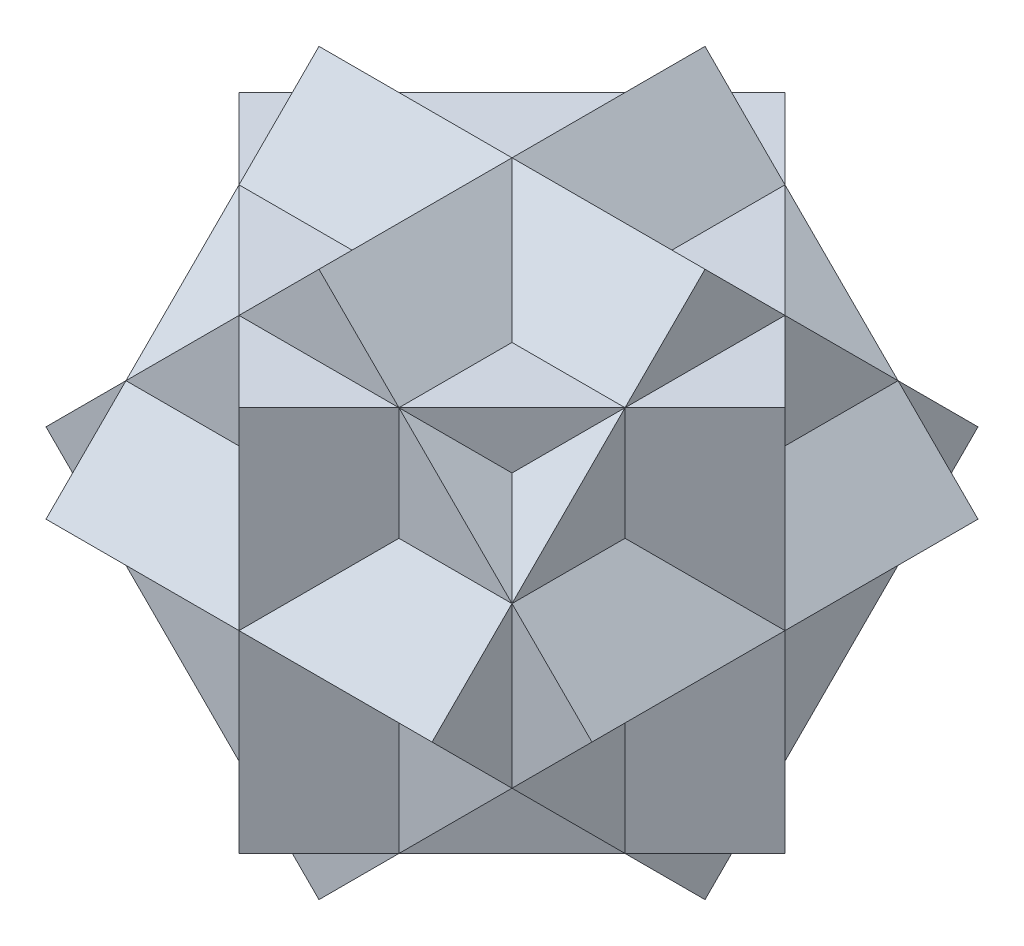
SolidWorks part; units mm, degrees
ref_plane "Front Plane" through (0, 0, 0) normal (0, 0, 1) x (1, 0, 0)
ref_plane "Top Plane" through (0, 0, 0) normal (0, 1, 0) x (1, 0, 0)
ref_plane "Right Plane" through (0, 0, 0) normal (1, 0, 0) x (0, 0, -1)
sketch "Sketch3" plane through (0, 0, 0) normal (0, 0, 1) x (1, 0, 0)
  line L0 (-160.803, 0) -> (0, 160.803)
  line L1 (-160.803, 0) -> (0, -160.803)
  line L2 (0, 160.803) -> (160.803, 0)
  line L3 (0, -160.803) -> (160.803, 0)
  line L4 (-160.803, 0) -> (160.803, 0) construction
  line L5 (0, 160.803) -> (0, -160.803) construction
  point P1 (0, 0)
  dimension "D1" = 227.4098
sketch "Sketch4" plane through (0, 0, 0) normal (0, 1, 0) x (1, 0, 0)
  line L0 (-160.803, 0) -> (0, 160.803)
  line L1 (-160.803, 0) -> (0, -160.803)
  line L2 (0, 160.803) -> (160.803, 0)
  line L3 (0, -160.803) -> (160.803, 0)
  line L4 (-160.803, 0) -> (160.803, 0) construction
  line L5 (0, 160.803) -> (0, -160.803) construction
  point P1 (0, 0)
sketch "Sketch5" plane through (0, 0, 0) normal (1, 0, 0) x (0, 0, -1)
  line L0 (-160.803, 0) -> (0, 160.803)
  line L1 (-160.803, 0) -> (0, -160.803)
  line L2 (0, 160.803) -> (160.803, 0)
  line L3 (0, -160.803) -> (160.803, 0)
  line L4 (-160.803, 0) -> (160.803, 0) construction
  line L5 (0, 160.803) -> (0, -160.803) construction
  line L6 (0, 160.803) -> (0, -160.803) construction
  point P1 (0, 0)
extrude "Boss-Extrude1" add sketch "Sketch3" along normal mid plane 227.4098
extrude "Boss-Extrude2" add sketch "Sketch4" along normal mid plane 227.4098
extrude "Boss-Extrude3" add sketch "Sketch5" along normal mid plane 227.4098
sketch "Sketch6" plane through (80.4015, -80.4015, 0) normal (0.7071, -0.7071, 0) x (0, 0, -1)
  line L16 (-4.9069, -111.1649) -> (-48.4129, -49.6381)
  line L17 (-48.4129, -49.6381) -> (-111.1649, -49.6381)
  line L18 (-111.1649, -49.6381) -> (-111.1649, -111.1649)
  line L19 (-111.1649, -111.1649) -> (-4.9069, -111.1649)
  line L20 (-4.9069, -111.1649) -> (-48.4129, -49.6381)
  line L21 (-48.4129, -49.6381) -> (-111.1649, -49.6381)
  line L22 (-111.1649, -49.6381) -> (-111.1649, -111.1649)
  line L23 (-111.1649, -111.1649) -> (-4.9069, -111.1649)
  dimension "D2" = 2.54
sketch "Sketch8" plane through (-80.4015, -80.4015, 0) normal (-0.7071, -0.7071, 0) x (0, 0, 1)
  line L8 (48.4129, -49.6381) -> (4.9069, -111.1649)
  line L9 (4.9069, -111.1649) -> (111.1649, -111.1649)
  line L10 (111.1649, -111.1649) -> (111.1649, -49.6381)
  line L11 (111.1649, -49.6381) -> (48.4129, -49.6381)
  line L12 (48.4129, -49.6381) -> (4.9069, -111.1649)
  line L13 (4.9069, -111.1649) -> (111.1649, -111.1649)
  line L14 (111.1649, -111.1649) -> (111.1649, -49.6381)
  line L15 (111.1649, -49.6381) -> (48.4129, -49.6381)
  dimension "D1" = 2.54
sketch "Sketch11" plane through (0, 0, 113.7049) normal (0, 0, 1) x (1, 0, 0)
  line L0 (0, -157.2109) -> (40.966, -116.2449)
  line L1 (40.966, -116.2449) -> (-40.966, -116.2449)
  line L2 (-40.966, -116.2449) -> (0, -157.2109)
  line L3 (0, -160.803) -> (47.0981, -113.7049)
  line L4 (47.0981, -113.7049) -> (-47.0981, -113.7049)
  line L5 (-47.0981, -113.7049) -> (0, -160.803)
  line L6 (0, -160.803) -> (47.0981, -113.7049) construction
  line L7 (47.0981, -113.7049) -> (-47.0981, -113.7049) construction
  line L8 (-47.0981, -113.7049) -> (0, -160.803) construction
  dimension "D2" = 2.54
sketch "Sketch12" plane through (0, -113.7049, 0) normal (0, -1, 0) x (1, 0, 0)
  line L0 (0, 159.0069) -> (-44.0321, 114.9749)
  line L1 (-44.0321, 114.9749) -> (44.0321, 114.9749)
  line L2 (44.0321, 114.9749) -> (0, 159.0069)
  line L3 (-47.0981, 113.7049) -> (47.0981, 113.7049)
  line L4 (47.0981, 113.7049) -> (0, 160.803)
  line L5 (0, 160.803) -> (-47.0981, 113.7049)
  line L6 (-47.0981, 113.7049) -> (47.0981, 113.7049) construction
  line L7 (47.0981, 113.7049) -> (0, 160.803) construction
  line L8 (0, 160.803) -> (-47.0981, 113.7049) construction
  point P6 (0, 154.8281)
  dimension "D2" = 2.54
sketch "Sketch13" plane through (0, -80.4015, 80.4015) normal (0, -0.7071, 0.7071) x (1, 0, 0)
  line L0 (111.1649, -49.6381) -> (48.4129, -49.6381)
  line L1 (48.4129, -49.6381) -> (4.9069, -111.1649)
  line L2 (4.9069, -111.1649) -> (111.1649, -111.1649)
  line L3 (111.1649, -111.1649) -> (111.1649, -49.6381)
  line L4 (113.7049, -113.7049) -> (113.7049, -47.0981)
  line L5 (113.7049, -47.0981) -> (47.0981, -47.0981)
  line L6 (47.0981, -47.0981) -> (0, -113.7049)
  line L7 (0, -113.7049) -> (113.7049, -113.7049)
  line L8 (113.7049, -113.7049) -> (113.7049, -47.0981) construction
  line L9 (113.7049, -47.0981) -> (47.0981, -47.0981) construction
  line L10 (47.0981, -47.0981) -> (0, -113.7049) construction
  line L11 (0, -113.7049) -> (113.7049, -113.7049) construction
  dimension "D2" = 2.54
sketch "Sketch14" plane through (0, -113.7049, 0) normal (0, -1, 0) x (1, 0, 0)
  line L0 (49.6381, 107.5728) -> (49.6381, 49.6381)
  line L1 (49.6381, 49.6381) -> (107.5728, 49.6381)
  line L2 (107.5728, 49.6381) -> (49.6381, 107.5728)
  line L3 (47.0981, 47.0981) -> (113.7049, 47.0981)
  line L4 (113.7049, 47.0981) -> (47.0981, 113.7049)
  line L5 (47.0981, 113.7049) -> (47.0981, 47.0981)
  line L6 (47.0981, 47.0981) -> (113.7049, 47.0981) construction
  line L7 (113.7049, 47.0981) -> (47.0981, 113.7049) construction
  line L8 (47.0981, 113.7049) -> (47.0981, 47.0981) construction
  dimension "D2" = 2.54
sketch "Sketch15" plane through (80.4015, 0, 80.4015) normal (0.7071, 0, 0.7071) x (0.7071, 0, -0.7071)
  line L0 (39.1066, -111.1649) -> (0, -83.5123)
  line L1 (0, -83.5123) -> (-39.1066, -111.1649)
  line L2 (-39.1066, -111.1649) -> (39.1066, -111.1649)
  line L3 (47.0981, -113.7049) -> (0, -80.4015)
  line L4 (0, -80.4015) -> (-47.0981, -113.7049)
  line L5 (-47.0981, -113.7049) -> (47.0981, -113.7049)
  line L6 (47.0981, -113.7049) -> (0, -80.4015) construction
  line L7 (0, -80.4015) -> (-47.0981, -113.7049) construction
  line L8 (-47.0981, -113.7049) -> (47.0981, -113.7049) construction
  dimension "D2" = 2.54
sketch "Sketch16" plane through (80.4015, -80.4015, 0) normal (0.7071, -0.7071, 0) x (0, 0, -1)
  line L0 (-83.5123, 0) -> (-111.1649, 39.1066)
  line L1 (-111.1649, 39.1066) -> (-111.1649, -39.1066)
  line L2 (-111.1649, -39.1066) -> (-83.5123, 0)
  line L3 (-80.4015, 0) -> (-113.7049, 47.0981)
  line L4 (-113.7049, 47.0981) -> (-113.7049, -47.0981)
  line L5 (-113.7049, -47.0981) -> (-80.4015, 0)
  line L6 (-80.4015, 0) -> (-113.7049, 47.0981) construction
  line L7 (-113.7049, 47.0981) -> (-113.7049, -47.0981) construction
  line L8 (-113.7049, -47.0981) -> (-80.4015, 0) construction
  dimension "D2" = 2.54
sketch "Sketch17" plane through (80.4015, 0, 80.4015) normal (0.7071, 0, 0.7071) x (0.7071, 0, -0.7071)
  line L0 (-49.6381, -48.4129) -> (-111.1649, -4.9069)
  line L1 (-111.1649, -4.9069) -> (-111.1649, -111.1649)
  line L2 (-111.1649, -111.1649) -> (-49.6381, -111.1649)
  line L3 (-49.6381, -111.1649) -> (-49.6381, -48.4129)
  line L4 (-47.0981, -47.0981) -> (-113.7049, 0)
  line L5 (-113.7049, 0) -> (-113.7049, -113.7049)
  line L6 (-113.7049, -113.7049) -> (-47.0981, -113.7049)
  line L7 (-47.0981, -113.7049) -> (-47.0981, -47.0981)
  line L8 (-47.0981, -47.0981) -> (-113.7049, 0) construction
  line L9 (-113.7049, 0) -> (-113.7049, -113.7049) construction
  line L10 (-113.7049, -113.7049) -> (-47.0981, -113.7049) construction
  line L11 (-47.0981, -113.7049) -> (-47.0981, -47.0981) construction
  dimension "D2" = 2.54
sketch "Sketch19" plane through (0, 0, 113.7049) normal (0, 0, 1) x (1, 0, 0)
  line L0 (49.6381, -49.6381) -> (49.6381, -107.5728)
  line L1 (49.6381, -107.5728) -> (107.5728, -49.6381)
  line L2 (107.5728, -49.6381) -> (49.6381, -49.6381)
  line L3 (47.0981, -113.7049) -> (113.7049, -47.0981)
  line L4 (113.7049, -47.0981) -> (47.0981, -47.0981)
  line L5 (47.0981, -47.0981) -> (47.0981, -113.7049)
  line L6 (47.0981, -113.7049) -> (113.7049, -47.0981) construction
  line L7 (113.7049, -47.0981) -> (47.0981, -47.0981) construction
  line L8 (47.0981, -47.0981) -> (47.0981, -113.7049) construction
  dimension "D2" = 2.54
equation "\"side_length\"= 4 * 2.238285"
equation "\"D1@Sketch3\"=\"side_length\""
equation "\"D1@Boss-Extrude1\"=\"side_length\""
equation "\"D1@Boss-Extrude2\"=\"side_length\""
equation "\"D1@Boss-Extrude3\"=\"side_length\""
equation "\"Joiner_spacing\"=0.1"
equation "\"D1@Sketch8\"=\"Joiner_spacing\""
equation "\"D2@Sketch11\"=\"Joiner_spacing\""
equation "\"D2@Sketch12\"=\"Joiner_spacing\""
equation "\"D2@Sketch13\"=\"Joiner_spacing\""
equation "\"D2@Sketch14\"=\"Joiner_spacing\""
equation "\"D2@Sketch15\"=\"Joiner_spacing\""
equation "\"D2@Sketch16\"=\"Joiner_spacing\""
equation "\"D2@Sketch17\"=\"Joiner_spacing\""
equation "\"D2@Sketch19\"=\"Joiner_spacing\""
